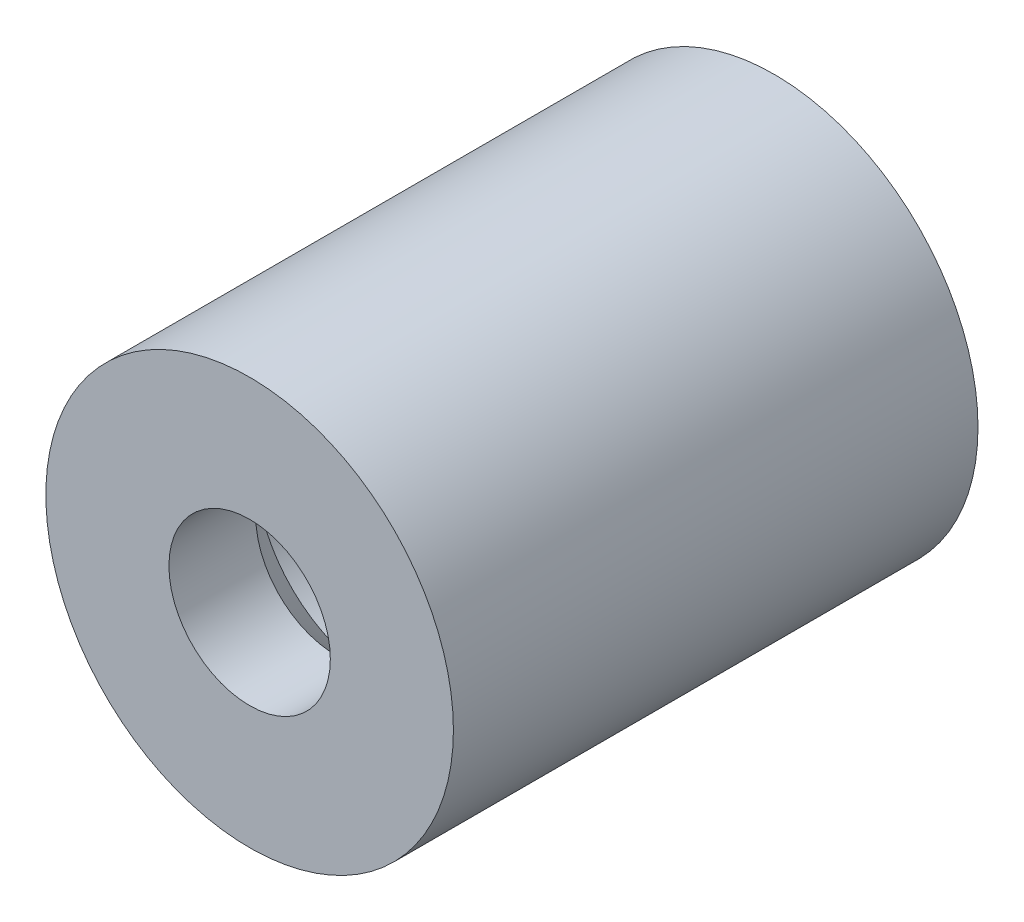
SolidWorks part; units mm, degrees
ref_plane "Front Plane" through (0, 0, 0) normal (1, 0, 0) x (0, 1, 0)
ref_plane "Top Plane" through (0, 0, 0) normal (0, 0, 1) x (0, 1, 0)
ref_plane "Right Plane" through (0, 0, 0) normal (0, 1, 0) x (-1, 0, 0)
sketch "Sketch1" plane through (0, 0, 0) normal (0, 0, 1) x (0, 1, 0)
  circle A0 centre (0, 0) radius 3.05
  circle A1 centre (0, 0) radius 5.05
  circle A2 centre (0, 0) radius 2
  dimension "D1" = 6.1
  dimension "D2" = 2
  dimension "D3" = 4
extrude "Boss-Extrude1" add sketch "Sketch1" along normal blind 11 contours A1 A0 region at (0, -4.9072, 0)
extrude "Boss-Extrude2" add sketch "Sketch1<3>" along normal blind 2 from surface contours A0 A2 | A1 A0 region at (0, -2.9637, 0) region at (0, -4.9072, 0) starting at face at (3.05, 0, 11)
sketch "Sketch1<3>" plane through (0, 0, 0) normal (0, 0, 1) x (0, 1, 0) same geometry as "Sketch1"
sketch "Sketch2" plane through (0, 0, 0) normal (0, 1, 0) x (-1, 0, 0)
  line L0 (0, 11) -> (0, 0) construction
  line L3 (2, 13) -> (-2, 13) construction
  circle A0 centre (0, 3) radius 1.6
  dimension "D1" = 3.2
  dimension "D2" = 10
extrude "Cut-Extrude1" cut sketch "Sketch2" against normal up to next
chamfer "Chamfer1" distance 1.2 angle 45 1 edges at (3.05, 0, 11)
